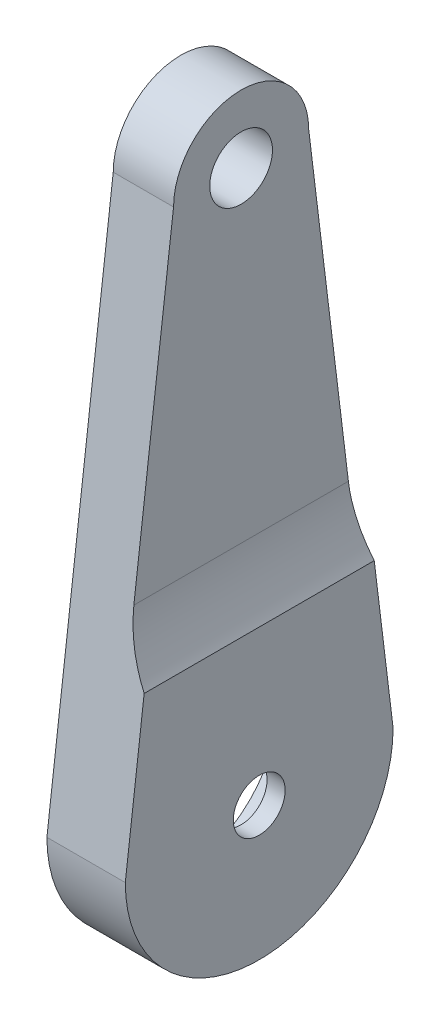
SolidWorks part; units mm, degrees
ref_plane "Front Plane" through (0, 0, 0) normal (1, 0, 0) x (0, 1, 0)
ref_plane "Top Plane" through (0, 0, 0) normal (0, 0, 1) x (0, 1, 0)
ref_plane "Right Plane" through (0, 0, 0) normal (0, 1, 0) x (-1, 0, 0)
sketch "Sketch2" plane through (0, 0, 0) normal (1, 0, 0) x (0, 1, 0)
  line L0 (0, 0) -> (8.1, 0)
  line L3 (42.4, 0) -> (45, 0)
  line L4 (0, 11.1) -> (45, 5.6)
  line L5 (45, -5.6) -> (0, -11.1)
  circle A0 centre (0, 0) radius 8.1
  circle A1 centre (45, 0) radius 2.6
  arc A2 (0, 11.1) -> (0, -11.1) centre (0, 0) ccw
  arc A3 (45, -5.6) -> (45, 5.6) centre (45, 0) ccw
  circle A4 centre (0, 0) radius 11.1 construction
  circle A5 centre (45, 0) radius 5.6 construction
  dimension "D1" = 16.2
  dimension "D2" = 5.2
  dimension "D4" = 3
  dimension "D3" = 3
extrude "Boss-Extrude1" add sketch "Sketch2" along normal mid plane 5 contours L5 A3 L4 A2 A0 A1 region at (0, 20.2348, 0)
sketch "Sketch3" plane through (-2.5, 0, 0) normal (1, 0, 0) x (0, 1, 0)
  circle A0 centre (0, 0) radius 4.25
  dimension "D1" = 8.5
extrude "Cut-Extrude1" [suppressed] cut sketch "Sketch3" along normal blind 0.8
sketch "Sketch5" plane through (2.5, 0, 0) normal (1, 0, 0) x (0, 1, 0)
  line L3 (12.7947, 9.5362) -> (12.7947, -9.5362)
  line L4 (0, 11.1) -> (45, 5.6) construction
  line L5 (45, -5.6) -> (0, -11.1) construction
  line L6 (12.7947, -9.5362) -> (0, -11.1)
  line L7 (0, 11.1) -> (12.7947, 9.5362)
  arc A2 (0, 11.1) -> (0, -11.1) centre (0, 0) ccw construction
  arc A3 (0, 11.1) -> (0, -11.1) centre (0, 0) ccw
  circle A4 centre (0, 0) radius 2.15
  dimension "D1" = 4.3
extrude "Boss-Extrude3" add sketch "Sketch5" along normal blind 1.5
fillet "Fillet2" radius 10 1 edges at (2.5, 12.7947, 0)
